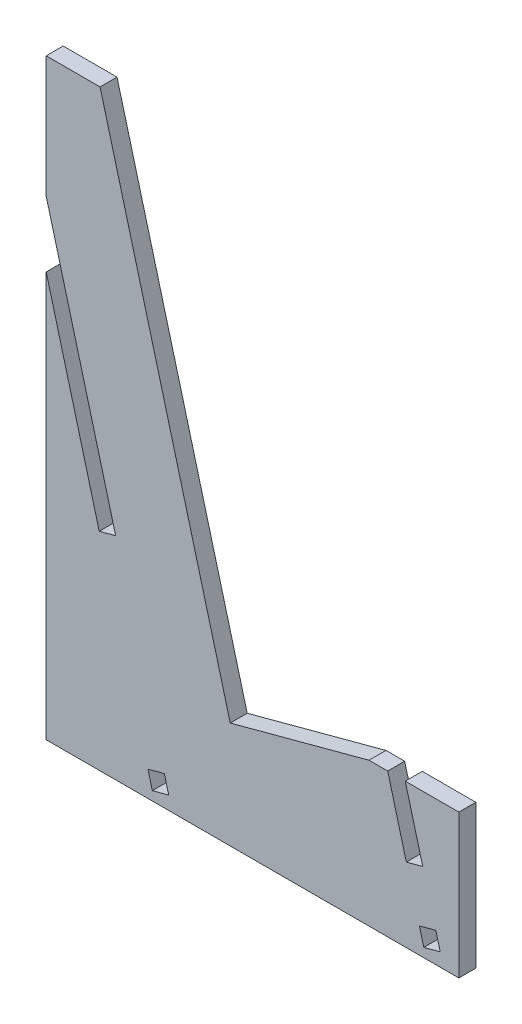
SolidWorks part; units mm, degrees
ref_plane "Front Plane" through (0, 0, 0) normal (0, 0, 1) x (1, 0, 0)
ref_plane "Top Plane" through (0, 0, 0) normal (0, 1, 0) x (1, 0, 0)
ref_plane "Right Plane" through (0, 0, 0) normal (1, 0, 0) x (0, 0, -1)
sketch "Sketch1" plane through (0, 0, 0) normal (0, 0, 1) x (1, 0, 0)
  line L0 (-38.029, 83.6028) -> (-38.029, -21.094)
  line L1 (-38.029, -21.094) -> (34.9145, -21.094)
  line L2 (34.9145, -21.094) -> (34.9145, 4.306)
  line L3 (34.9145, 4.306) -> (19.0395, 4.306)
  line L4 (19.0395, 4.306) -> (-5.495, -2.268)
  line L5 (-5.495, -2.268) -> (-28.504, 83.6028)
  line L6 (-28.504, 83.6028) -> (-38.029, 83.6028)
  dimension "D1" = 25.4
  dimension "D2" = 25.4
  dimension "D3" = 88.9
  dimension "D4" = 15.875
  dimension "D5" = 9.525
  dimension "D6" = 15
extrude "Boss-Extrude1" add sketch "Sketch1" along normal blind 3
sketch "Sketch2" plane through (0, 0, 3) normal (0, 0, 1) x (1, 0, 0)
  line L0 (-19.2646, -19.5065) -> (-16.3669, -18.7301)
  line L1 (-19.2646, -19.5065) -> (-20.0411, -16.6087)
  line L2 (-16.3669, -18.7301) -> (-17.1433, -15.8323)
  line L3 (-20.0411, -16.6087) -> (-17.1433, -15.8323)
  line L4 (-19.2646, -19.5065) -> (-17.1433, -15.8323) construction
  line L5 (-16.3669, -18.7301) -> (-20.0411, -16.6087) construction
  line L6 (-5.495, -2.268) -> (-28.504, 83.6028) construction
  line L7 (-38.029, -21.094) -> (34.9145, -21.094) construction
  line L8 (-28.6468, 15.5083) -> (-25.7491, 16.2848)
  line L9 (-28.6468, 15.5083) -> (-38.029, 50.5231)
  line L10 (-25.7491, 16.2848) -> (-35.1312, 51.2996)
  line L11 (-38.029, 50.5231) -> (-35.1312, 51.2996) construction
  line L12 (-28.6468, 15.5083) -> (-35.1312, 51.2996) construction
  line L13 (-25.7491, 16.2848) -> (-38.029, 50.5231) construction
  line L14 (-38.029, 83.6028) -> (-38.029, -21.094) construction
  line L15 (-19.2646, -19.5065) -> (-38.029, 50.5231) construction
  line L16 (-35.1312, 51.2996) -> (-38.029, 62.1142)
  line L17 (-38.029, 62.1142) -> (-38.029, 50.5231)
  line L18 (-30.6972, 28.9558) -> (-22.9324, -0.0227) construction
  point P0 (-28.6468, 15.5083)
  point P1 (-18.204, -17.6694)
  point P10 (-31.889, 33.4039)
  line M12 (-38.029, 83.6028) -> (-38.029, -21.094)
  dimension "D1" = 3
  dimension "D2" = 3
  dimension "D3" = 1.5875
  dimension "D4" = 3
  dimension "D5" = 72.5
extrude "Cut-Extrude1" cut sketch "Sketch2" against normal through all contours L10 L16 L9 L8 M12 | L3 L1 L0 L2 region at (-18.204, -17.6694, 3) region at (-32.5812, 36.2455, 3)
sketch "Sketch3" plane through (0, 0, 3) normal (0, 0, 1) x (1, 0, 0)
  line L0 (28.7184, -19.5065) -> (31.6162, -18.7301)
  line L1 (28.7184, -19.5065) -> (27.9419, -16.6087)
  line L2 (31.6162, -18.7301) -> (30.8397, -15.8323)
  line L3 (27.9419, -16.6087) -> (30.8397, -15.8323)
  line L4 (28.7184, -19.5065) -> (30.8397, -15.8323) construction
  line L5 (31.6162, -18.7301) -> (27.9419, -16.6087) construction
  line L6 (25.6321, -7.9885) -> (28.5299, -7.212)
  line L7 (25.6321, -7.9885) -> (22.5459, 3.5295)
  line L8 (28.5299, -7.212) -> (25.4437, 4.306)
  line L9 (22.5459, 3.5295) -> (25.4437, 4.306) construction
  line L10 (25.6321, -7.9885) -> (25.4437, 4.306) construction
  line L11 (28.5299, -7.212) -> (22.5459, 3.5295) construction
  line L12 (-5.495, -2.268) -> (-28.504, 83.6028) construction
  line L15 (34.9145, 4.306) -> (19.0395, 4.306) construction
  line L16 (22.5459, 3.5295) -> (22.3378, 4.306)
  line L17 (22.3378, 4.306) -> (25.4437, 4.306)
  line L18 (22.5459, 3.5295) -> (28.7184, -19.5065) construction
  line L19 (19.0395, 4.306) -> (22.3378, 4.306) construction
  line L20 (31.6162, -18.7301) -> (34.9145, -18.7301) construction
  line L21 (34.9145, -21.094) -> (34.9145, 4.306) construction
  point P0 (25.6321, -7.9885)
  point P1 (29.779, -17.6694)
  point P2 (25.5379, -1.8413)
  dimension "D1" = 3
  dimension "D2" = 3
extrude "Cut-Extrude2" cut sketch "Sketch3" against normal through all
equation "\"thick\"= 3mm"
equation "\"D1@Boss-Extrude1\"=\"thick\""
equation "\"D1@Sketch2\"=\"thick\""
equation "\"D2@Sketch2\"=\"thick\""
equation "\"D4@Sketch2\"=\"thick\""
equation "\"D1@Sketch3\"=\"thick\""
equation "\"D2@Sketch3\"=\"thick\""
